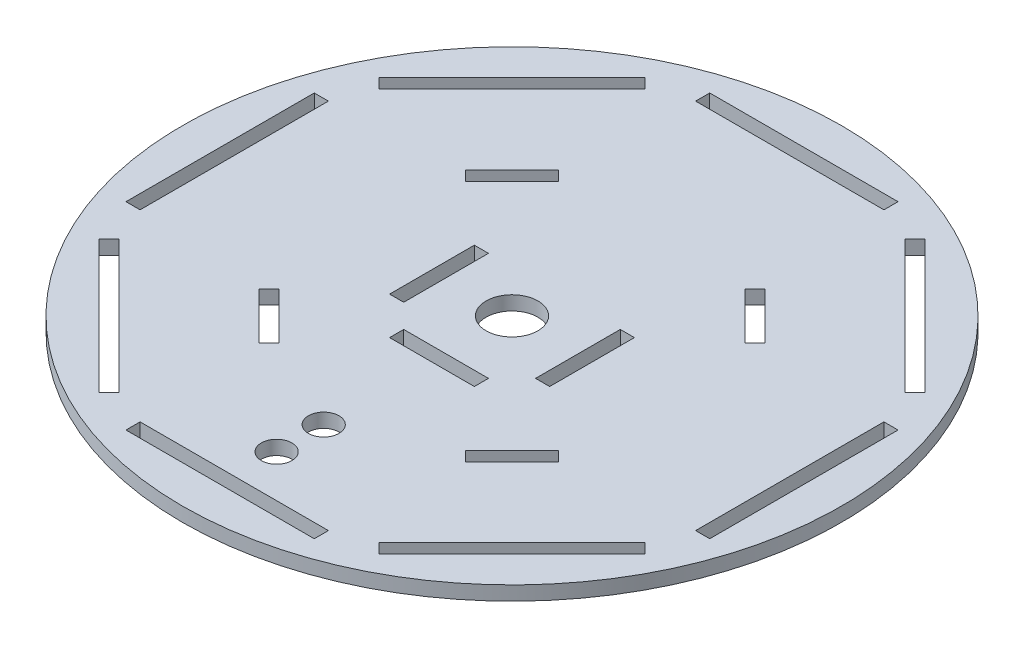
SolidWorks part; units mm, degrees
ref_plane "Alzado" through (0, 0, 0) normal (0, 0, 1) x (1, 0, 0)
ref_plane "Planta" through (0, 0, 0) normal (0, 1, 0) x (1, 0, 0)
ref_plane "Vista lateral" through (0, 0, 0) normal (1, 0, 0) x (0, 0, -1)
sketch "Croquis1" plane through (0, 0, 0) normal (0, 1, 0) x (1, 0, 0)
  line L0 (24.7487, 24.7487) -> (29.6985, 19.799)
  line L1 (29.6985, 19.799) -> (31.8198, 21.9203)
  line L2 (31.8198, 21.9203) -> (21.9203, 31.8198)
  line L3 (19.799, 29.6985) -> (21.9203, 31.8198)
  line L4 (24.7487, 24.7487) -> (19.799, 29.6985)
  line L5 (24.7487, -24.7487) -> (19.799, -29.6985)
  line L6 (19.799, -29.6985) -> (21.9203, -31.8198)
  line L7 (21.9203, -31.8198) -> (31.8198, -21.9203)
  line L8 (29.6985, -19.799) -> (31.8198, -21.9203)
  line L9 (24.7487, -24.7487) -> (29.6985, -19.799)
  line L10 (0, 0) -> (-24.7487, 24.7487) construction
  line L11 (-24.7487, 24.7487) -> (-19.799, 29.6985)
  line L12 (-19.799, 29.6985) -> (-21.9203, 31.8198)
  line L13 (-24.7487, -24.7487) -> (-29.6985, -19.799)
  line L14 (-29.6985, -19.799) -> (-31.8198, -21.9203)
  line L15 (-31.8198, -21.9203) -> (-21.9203, -31.8198)
  line L16 (-19.799, -29.6985) -> (-21.9203, -31.8198)
  line L17 (-24.7487, -24.7487) -> (-19.799, -29.6985)
  line L18 (0, 0) -> (0, -50) construction
  line L20 (-14, 0) -> (-14, 9)
  line L21 (-14, 9) -> (-17, 9)
  line L22 (-17, 9) -> (-17, -9)
  line L23 (-21.9203, 31.8198) -> (-31.8198, 21.9203)
  line L24 (-24.7487, 24.7487) -> (-29.6985, 19.799)
  line L25 (-29.6985, 19.799) -> (-31.8198, 21.9203)
  line L26 (-17, -9) -> (-14, -9)
  line L27 (-14, -9) -> (-14, 0)
  line L33 (14, -9) -> (17, -9)
  line L34 (14, 0) -> (14, -9)
  line L35 (14, 9) -> (14, 0)
  line L36 (17, 9) -> (14, 9)
  line L37 (17, -9) -> (17, 9)
  line L38 (-9, -14) -> (-9, -17)
  line L39 (0, -14) -> (-9, -14)
  line L40 (9, -14) -> (0, -14)
  line L41 (0, 0) -> (0, 62) construction
  line L42 (0, 62) -> (20, 62)
  line L43 (20, 62) -> (20, 59)
  line L44 (20, 59) -> (-20, 59)
  line L45 (-20, 59) -> (-20, 62)
  line L46 (-20, 62) -> (0, 62)
  line L47 (55.8614, 27.5772) -> (27.5772, 55.8614)
  line L48 (27.5772, 55.8614) -> (29.6985, 57.9828)
  line L49 (29.6985, 57.9828) -> (43.8406, 43.8406)
  line L50 (43.8406, 43.8406) -> (57.9828, 29.6985)
  line L51 (57.9828, 29.6985) -> (55.8614, 27.5772)
  line L52 (59, -20) -> (59, 20)
  line L53 (59, 20) -> (62, 20)
  line L54 (62, 20) -> (62, 0)
  line L55 (62, 0) -> (62, -20)
  line L56 (62, -20) -> (59, -20)
  line L57 (27.5772, -55.8614) -> (55.8614, -27.5772)
  line L58 (55.8614, -27.5772) -> (57.9828, -29.6985)
  line L59 (57.9828, -29.6985) -> (43.8406, -43.8406)
  line L60 (43.8406, -43.8406) -> (29.6985, -57.9828)
  line L61 (29.6985, -57.9828) -> (27.5772, -55.8614)
  line L62 (-20, -59) -> (20, -59)
  line L63 (20, -59) -> (20, -62)
  line L64 (20, -62) -> (0, -62)
  line L65 (0, -62) -> (-20, -62)
  line L66 (-20, -62) -> (-20, -59)
  line L67 (-55.8614, -27.5772) -> (-27.5772, -55.8614)
  line L68 (-27.5772, -55.8614) -> (-29.6985, -57.9828)
  line L69 (-29.6985, -57.9828) -> (-43.8406, -43.8406)
  line L70 (-43.8406, -43.8406) -> (-57.9828, -29.6985)
  line L71 (-57.9828, -29.6985) -> (-55.8614, -27.5772)
  line L72 (-59, 20) -> (-59, -20)
  line L73 (-59, -20) -> (-62, -20)
  line L74 (-62, -20) -> (-62, 0)
  line L75 (-62, 0) -> (-62, 20)
  line L76 (-62, 20) -> (-59, 20)
  line L77 (-27.5772, 55.8614) -> (-55.8614, 27.5772)
  line L78 (-55.8614, 27.5772) -> (-57.9828, 29.6985)
  line L79 (-57.9828, 29.6985) -> (-43.8406, 43.8406)
  line L80 (-43.8406, 43.8406) -> (-29.6985, 57.9828)
  line L81 (-29.6985, 57.9828) -> (-27.5772, 55.8614)
  line L82 (9, -17) -> (9, -14)
  line L83 (-9, -17) -> (9, -17)
  line L85 (9, 14) -> (9, 17) [skipped]
  line L86 (0, 14) -> (9, 14) [skipped]
  line L87 (9, 17) -> (-9, 17) [skipped]
  line L88 (-9, 14) -> (0, 14) [skipped]
  line L89 (-9, 17) -> (-9, 14) [skipped]
  circle A0 centre (0, 0) radius 5.5
  circle A1 centre (0, -50) radius 3.25
  circle A2 centre (0, 0) radius 70
  circle A3 centre (0, -40) radius 3.25
  point P26 (0, 0)
  point P47 (0, 0)
  point P88 (0, 0)
  point P92 (0, 0)
  dimension "D2" = 7
  dimension "D3" = 140
  dimension "D7" = 6.5
  dimension "D19" = 11
  dimension "D21" = 6.5
  dimension "D4" = 35
  dimension "D5" = 4
  dimension "D6" = 50
  dimension "D8" = 14
  dimension "D9" = 7
  dimension "D10" = 3
  dimension "D11" = 9
  dimension "D12" = 3
  dimension "D14" = 4
  dimension "D15" = 20
  dimension "D16" = 3
  dimension "D17" = 40
  dimension "D13" = 18
  dimension "D20" = 40
  dimension "D18" = 8
extrude "Saliente-Extruir1" add sketch "Croquis1" along normal blind 3
